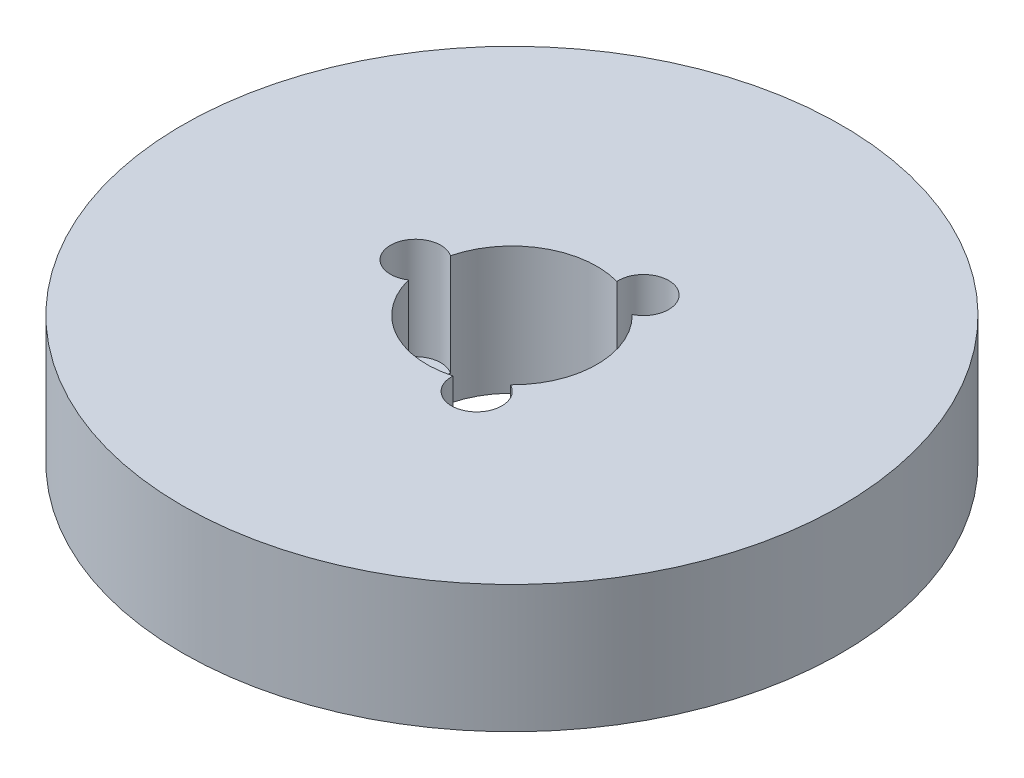
SolidWorks part; units mm, degrees
ref_plane "Front Plane" through (0, 0, 0) normal (0, 0, 1) x (1, 0, 0)
ref_plane "Top Plane" through (0, 0, 0) normal (0, 1, 0) x (1, 0, 0)
ref_plane "Right Plane" through (0, 0, 0) normal (1, 0, 0) x (0, 0, -1)
sketch "Sketch1" plane through (0, 0, 0) normal (0, 1, 0) x (1, 0, 0)
  circle A0 centre (0, 0) radius 77.5
  dimension "FLANGE_OD" = 155
extrude "Boss-Extrude1" add sketch "Sketch1" along normal blind 30
sketch "Sketch2" plane through (0, 0, 0) normal (0, 1, 0) x (1, 0, 0)
  circle A0 centre (0, 0) radius 20
  dimension "BORE_D" = 40
extrude "Cut-Extrude1" cut sketch "Sketch2" along normal through all
sketch "Sketch3" plane through (0, 30, 0) normal (0, 1, 0) x (1, 0, 0)
  circle A0 centre (0, 0) radius 22.6536 construction
  circle A1 centre (-22.6536, 0) radius 5.9214
  dimension "BOLT_D" = 11.8428
  dimension "BOLT_PCD" = 45.3072
extrude "Cut-Extrude2" cut sketch "Sketch3" against normal blind 23.925
pattern_circular "CirPattern1" count 3 over 360 about axis through (0, 0, 0) along (0, 1, 0) of "Cut-Extrude2"
